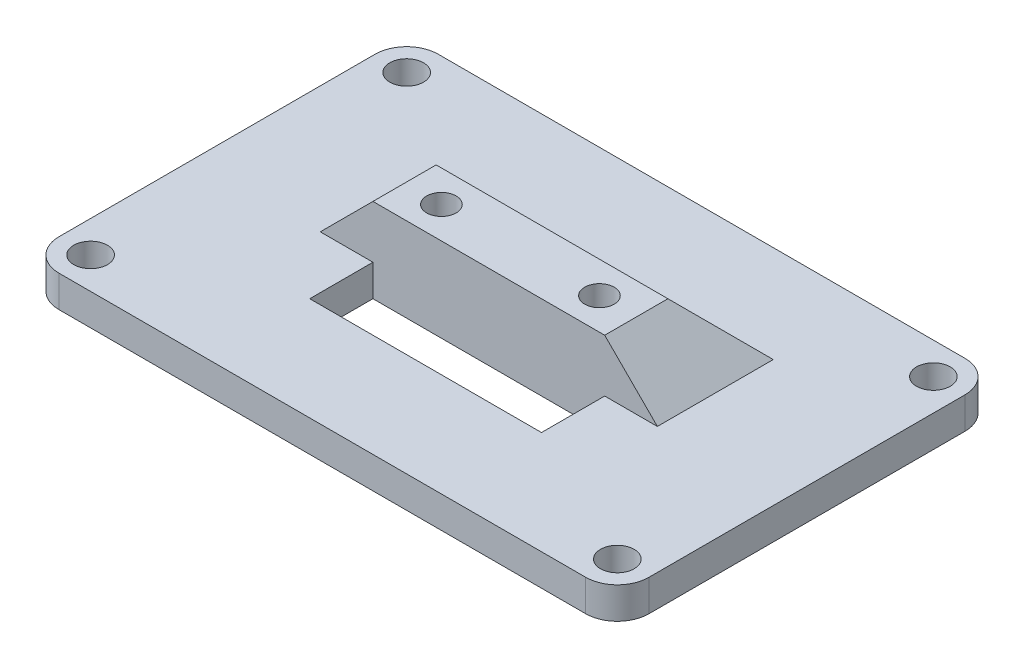
SolidWorks part; units mm, degrees
ref_plane "正面" through (0, 0, 0) normal (0, 0, 1) x (1, 0, 0)
ref_plane "平面" through (0, 0, 0) normal (0, 1, 0) x (1, 0, 0)
ref_plane "右側面" through (0, 0, 0) normal (1, 0, 0) x (0, 0, -1)
sketch "ｽｹｯﾁ1" plane through (0, 0, 0) normal (0, 1, 0) x (1, 0, 0)
  line L1 (-25, 15) -> (25, 15) construction
  line L2 (-25, 15) -> (-25, -15) construction
  line L3 (-25, -15) -> (25, -15) construction
  line L4 (25, 15) -> (25, -15) construction
  line L5 (-25, 15) -> (25, -15) construction
  line L6 (-25, -15) -> (25, 15) construction
  line L7 (-28, 18) -> (28, 18)
  line L8 (-28, 18) -> (-28, -18)
  line L9 (-28, -18) -> (28, -18)
  line L10 (28, 18) -> (28, -18)
  line L11 (-28, 18) -> (28, -18) construction
  line L12 (-28, -18) -> (28, 18) construction
  circle A0 centre (-25, 15) radius 1.6
  circle A1 centre (25, 15) radius 1.6
  circle A2 centre (25, -15) radius 1.6
  circle A3 centre (-25, -15) radius 1.6
  point P0 (0, 0)
  point P10 (0, 0)
  dimension "D1" = 50
  dimension "D3" = 3.2
  dimension "D2" = 30
  dimension "D4" = 3
  dimension "D5" = 3
extrude "ﾎﾞｽ - 押し出し1" add sketch "ｽｹｯﾁ1" along normal blind 3
fillet "ﾌｨﾚｯﾄ1" radius 3 4 edges at (-28, 1.5, -18) (28, 1.5, -18) (28, 1.5, 18) (-28, 1.5, 18)
sketch "ｽｹｯﾁ2" plane through (0, 3, 0) normal (0, 1, 0) x (1, 0, 0)
  line L0 (-7.5, 0.8) -> (7.5, 0.8) construction
  line L1 (0, 0) -> (0, 0.8) construction
  line L3 (-11, 3.8) -> (11, 3.8)
  line L4 (-11, 3.8) -> (-11, -2.2)
  line L5 (-11, -2.2) -> (11, -2.2)
  line L6 (11, 3.8) -> (11, -2.2)
  line L7 (-11, 3.8) -> (11, -2.2) construction
  line L8 (-11, -2.2) -> (11, 3.8) construction
  circle A0 centre (0, 0) radius 0.75 construction
  circle A1 centre (-7.5, 0.8) radius 1.4
  circle A2 centre (7.5, 0.8) radius 1.4
  point P5 (0, 0.8)
  dimension "D1" = 0.8
  dimension "D3" = 1.5
  dimension "D4" = 2.8
  dimension "D2" = 15
  dimension "D5" = 22
  dimension "D6" = 6
extrude "ﾎﾞｽ - 押し出し2" add sketch "ｽｹｯﾁ2" along normal blind 5
sketch "ｽｹｯﾁ3" plane through (0, 3, 0) normal (0, 1, 0) x (1, 0, 0)
  line L0 (11, -2.2) -> (11, 3.8) construction
  line L1 (-11, -8.2) -> (11, -8.2)
  line L2 (-11, -8.2) -> (-11, -2.2)
  line L3 (-11, -2.2) -> (11, -2.2)
  line L4 (11, -8.2) -> (11, -2.2)
  point P7 (0, 0)
  point P8 (-11, -2.2)
  dimension "D1" = 6
extrude "ｶｯﾄ - 押し出し1" cut sketch "ｽｹｯﾁ3" against normal through all
chamfer "面取り1" distance 5 angle 45 3 edges at (-11, 3, -0.8) (11, 3, -0.8) (0, 3, -3.8)
